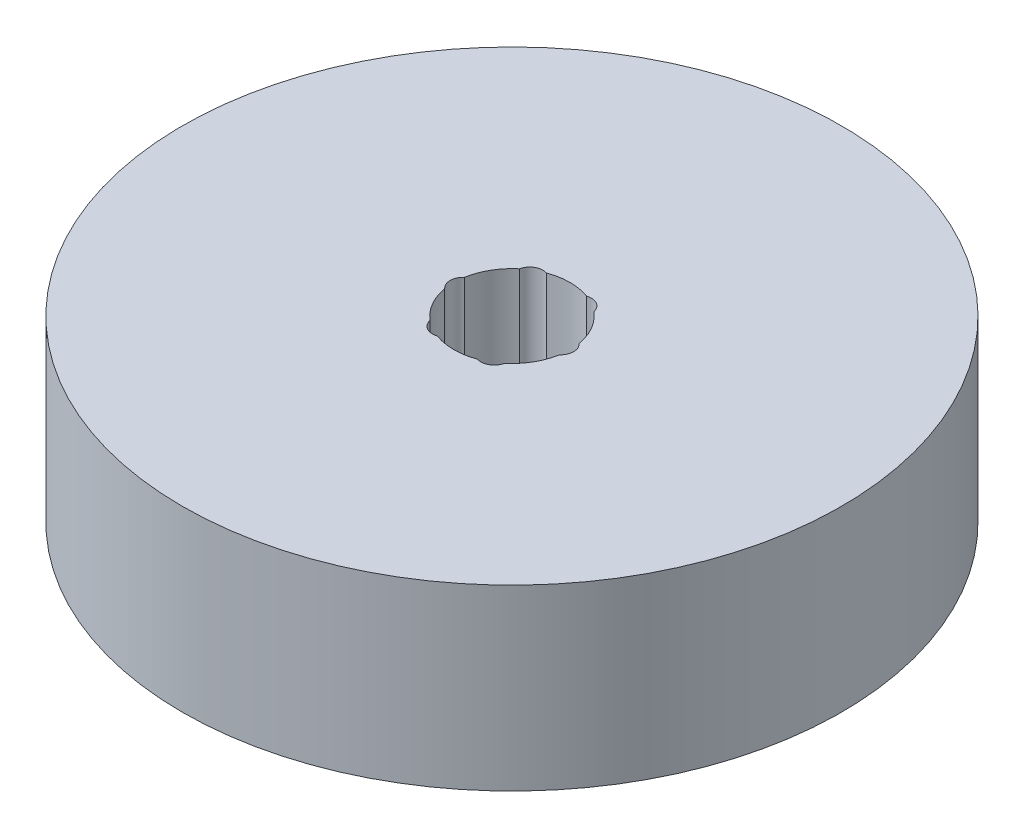
SolidWorks part; units mm, degrees
ref_plane "Front Plane" through (0, 0, 0) normal (0, 0, 1) x (1, 0, 0)
ref_plane "Top Plane" through (0, 0, 0) normal (0, 1, 0) x (1, 0, 0)
ref_plane "Right Plane" through (0, 0, 0) normal (1, 0, 0) x (0, 0, -1)
sketch "Sketch1" plane through (0, 0, 0) normal (0, 1, 0) x (1, 0, 0)
  circle A0 centre (0, 0) radius 42.5
  dimension "FLANGE_OD" = 85
extrude "Boss-Extrude1" add sketch "Sketch1" along normal blind 23
sketch "Sketch2" plane through (0, 0, 0) normal (0, 1, 0) x (1, 0, 0)
  circle A0 centre (0, 0) radius 7.5
  dimension "BORE_D" = 15
extrude "Cut-Extrude1" cut sketch "Sketch2" along normal through all
sketch "Sketch3" plane through (0, 23, 0) normal (0, 1, 0) x (1, 0, 0)
  circle A0 centre (0, 0) radius 6.2366 construction
  circle A1 centre (-6.2366, 0) radius 1.7219
  dimension "BOLT_D" = 3.4439
  dimension "BOLT_PCD" = 12.4732
extrude "Cut-Extrude2" cut sketch "Sketch3" against normal blind 21.0687
pattern_circular "CirPattern1" count 6 over 360 about axis through (0, 0, 0) along (0, 1, 0) of "Cut-Extrude2"
